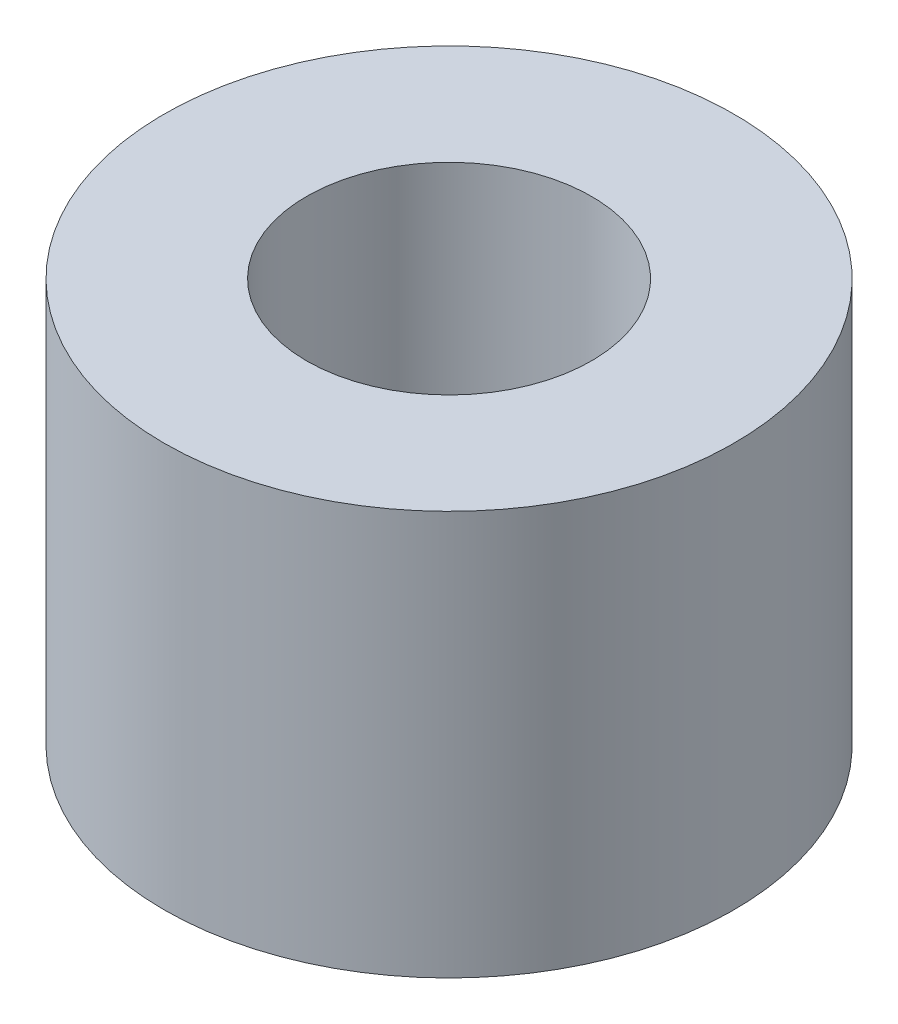
SolidWorks part; units mm, degrees
ref_plane "Front Plane" through (0, 0, 0) normal (0, 0, 1) x (1, 0, 0)
ref_plane "Top Plane" through (0, 0, 0) normal (0, 1, 0) x (1, 0, 0)
ref_plane "Right Plane" through (0, 0, 0) normal (1, 0, 0) x (0, 0, -1)
sketch "Sketch1" plane through (0, 0, 0) normal (0, 1, 0) x (1, 0, 0)
  circle A0 centre (0, 0) radius 5
  circle A1 centre (0, 0) radius 10
  dimension "D1" = 10
  dimension "D2" = 20
extrude "Boss-Extrude1" add sketch "Sketch1" along normal blind 14.18
